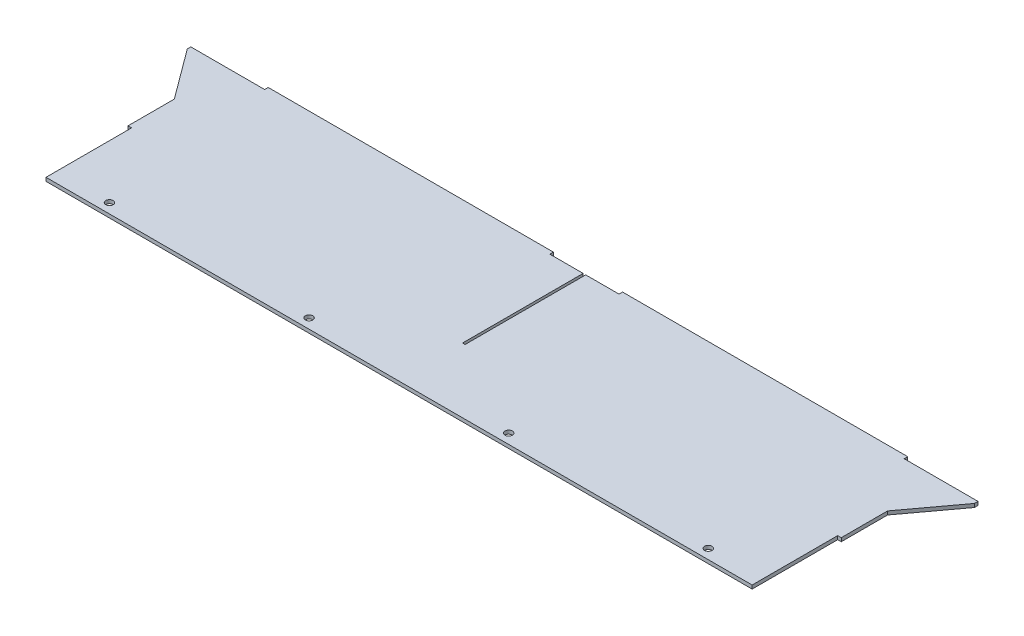
SolidWorks part; units mm, degrees
material "6061-T6 (SS)"
ref_plane "X-Y Datum" through (0, 0, 0) normal (0, 0, 1) x (1, 0, 0)
ref_plane "X-Z Datum" through (0, 0, 0) normal (0, 1, 0) x (1, 0, 0)
ref_plane "Y-Z Datum" through (0, 0, 0) normal (1, 0, 0) x (0, 0, -1)
sketch "Sketch1" plane through (0, 0, 0) normal (0, 1, 0) x (1, 0, 0)
  line L1 (-317.6778, 82.55) -> (317.6778, 82.55)
  line L2 (-317.6778, 82.55) -> (-317.6778, -82.55)
  line L3 (-317.6778, -82.55) -> (317.6778, -82.55)
  line L4 (317.6778, 82.55) -> (317.6778, -82.55)
  line L5 (-317.6778, 82.55) -> (317.6778, -82.55) construction
  line L6 (-317.6778, -82.55) -> (317.6778, 82.55) construction
  point P0 (0, 0)
  dimension "D1" = 635.3556
  dimension "D2" = 165.1
extrude "Boss-Extrude1" add sketch "Sketch1" along normal mid plane 3.175
sketch "Sketch2" plane through (0, 0, -82.55) normal (0, 0, -1) x (-1, 0, 0)
  line L20 (-317.6778, -1.5875) -> (317.6778, -1.5875) construction
  line L21 (-284.8229, -1.5875) -> (-30.8229, -1.5875)
  line L22 (30.8229, -1.5875) -> (284.8229, -1.5875)
  line L40 (30.8229, -1.5875) -> (30.8229, 1.5875)
  line L41 (30.8229, 1.5875) -> (284.8229, 1.5875)
  line L42 (284.8229, 1.5875) -> (284.8229, -1.5875)
  line L56 (-284.8229, -1.5875) -> (-284.8229, 1.5875)
  line L57 (-284.8229, 1.5875) -> (-30.8229, 1.5875)
  line L58 (-30.8229, 1.5875) -> (-30.8229, -1.5875)
extrude "Boss-Extrude2" add sketch "Sketch2" along normal blind 3.175
sketch "Sketch3" plane through (0, -1.5875, 0) normal (0, -1, 0) x (1, 0, 0)
  line L0 (317.6778, -82.55) -> (350.5784, -82.55)
  line L1 (350.5784, -82.55) -> (350.5784, -79.375)
  line L3 (350.5784, -79.375) -> (317.6778, -34.925)
  line L4 (317.6778, 82.55) -> (317.6778, -82.55) construction
  line L17 (317.6778, -82.55) -> (317.6778, 82.55)
  line L18 (317.6778, 82.55) -> (-317.6778, 82.55)
  line L19 (-317.6778, 82.55) -> (-317.6778, -82.55)
  line L20 (-317.6778, -82.55) -> (-284.8229, -82.55)
  line L21 (-284.8229, -82.55) -> (-284.8229, -85.725)
  line L22 (-284.8229, -85.725) -> (-30.8229, -85.725)
  line L23 (-30.8229, -85.725) -> (-30.8229, -82.55)
  line L24 (-30.8229, -82.55) -> (30.8229, -82.55)
  line L25 (30.8229, -82.55) -> (30.8229, -85.725)
  line L26 (30.8229, -85.725) -> (284.8229, -85.725)
  line L27 (284.8229, -85.725) -> (284.8229, -82.55)
  line L28 (284.8229, -82.55) -> (317.6778, -82.55)
  line L29 (317.6778, -82.55) -> (317.6778, -34.925)
  dimension "D1" = 32.9006
  dimension "D2" = 3.175
  dimension "D3" = 44.45
  dimension "D4" = 0
extrude "Boss-Extrude3" add sketch "Sketch3" against normal blind 3.175
mirror "Mirror1" about plane through (0, 0, 0) normal (1, 0, 0) of "Boss-Extrude3"
sketch "Sketch4" plane through (0, -1.5875, 0) normal (0, -1, 0) x (1, 0, 0)
  line L0 (-284.4038, 82.55) -> (-284.4038, 71.882)
  line L1 (-317.6778, 82.55) -> (317.6778, 82.55) construction
  line L2 (-284.4038, 71.882) -> (-317.6778, 71.882)
  line L3 (-317.6778, -34.925) -> (-317.6778, 82.55) construction
  circle A0 centre (-284.4038, 71.882) radius 3.675
extrude "Cut-Extrude1" [suppressed] cut sketch "Sketch4" against normal through all contours L2 A0 L0 | L0 A0 L2
pattern_linear "LPattern1" [suppressed] count 5 spacing 139.7 of bodies 107
sketch "Sketch5" plane through (0, -1.5875, 0) normal (0, -1, 0) x (1, 0, 0)
  line L0 (-317.6778, 82.55) -> (317.6778, 82.55) construction
  line L1 (-317.6778, -34.925) -> (-317.6778, 82.55) construction
  line L2 (-317.6778, 82.55) -> (317.6778, 82.55)
  line L3 (-317.6778, -34.925) -> (-317.6778, 82.55)
  line L4 (0, 127.4245) -> (0, -127.4245) construction
  line L5 (-317.6778, 82.55) -> (-314.5028, 82.55)
  line L6 (-317.6778, 82.55) -> (-317.6778, 6.35)
  line L7 (-317.6778, 6.35) -> (-314.5028, 6.35)
  line L8 (-314.5028, 82.55) -> (-314.5028, 6.35)
  line L9 (317.6778, 6.35) -> (314.5028, 6.35)
  line L10 (314.5028, 82.55) -> (314.5028, 6.35)
  line L11 (317.6778, -34.925) -> (317.6778, 82.55)
  line L12 (30.8229, -82.55) -> (-30.8229, -82.55) construction
  line L13 (30.8229, -82.55) -> (-30.8229, -82.55)
  line L14 (-1.143, -85.725) -> (-1.143, -82.55) construction
  line L15 (-1.143, -85.725) -> (-1.143, -82.55)
  line L17 (-1.143, -82.55) -> (1.143, -82.55)
  line L18 (-1.143, -82.55) -> (-1.143, 24.892)
  line L19 (-1.143, 24.892) -> (1.143, 24.892)
  line L20 (1.143, -82.55) -> (1.143, 24.892)
  point P10 (0, 0)
  line M10 (317.6778, -34.925) -> (317.6778, 82.55)
  line M11 (317.6778, 82.55) -> (-317.6778, 82.55)
  line M12 (-317.6778, 82.55) -> (-317.6778, -34.925)
  dimension "D1" = 3.175
  dimension "D2" = 76.2
  dimension "D3" = 2.286
  dimension "D4" = 107.442
extrude "Cut-Extrude2" cut sketch "Sketch5" against normal through all contours L19 L4 L17 L20 | L4 L19 L18 L13 | L8 L2 L7 M12 | L10 L9 M11 M10 region at (316.0903, -1.5875, 44.45) region at (0.5715, -1.5875, -28.829) region at (-0.5715, -1.5875, -28.829) region at (-316.0903, -1.5875, 44.45)
sketch "Sketch6" plane through (0, -1.5875, 0) normal (0, -1, 0) x (1, 0, 0)
  line L0 (-314.5028, 82.55) -> (314.5028, 82.55) construction
  line L1 (-314.5028, 82.55) -> (314.5028, 82.55)
  line L2 (0, 127.6954) -> (0, 37.4046) construction
  line L3 (314.5028, 82.55) -> (314.5028, 6.35) construction
  circle A0 centre (266.7, 73.8124) radius 3
  point P6 (0, 82.55)
  dimension "D1" = 6
  dimension "D2" = 8.7376
  dimension "D3" = 47.8028
hole_wizard "M6 Clearance Hole1" positions "Sketch7" profile "Sketch8" hole size "M6" standard "ANSI Metric" end condition through all
sketch "Sketch7" plane through (0, 1.5875, 0) normal (0, 1, 0) x (1, 0, 0)
  point P0 (266.7, -73.8124)
sketch "Sketch8" plane through (266.7, 1.5875, 73.8124) normal (1, 0, 0) x (0, 0, 1)
  line L0 (0, 0) -> (0, 3.175)
  line L1 (0, 3.175) -> (3.3, 3.175)
  line L2 (3.3, 3.175) -> (3.3, 0)
  line L5 (3.3, 0) -> (0, 0)
  line L11 (0, -6.35) -> (0, 107.95) construction
  dimension "Thru Hole Dia." = 6.6
  dimension "Thru Hole Depth" = 3.175
pattern_linear "LPattern2" count 4 spacing 177.8 along (-1, 0, 0) of "M6 Clearance Hole1"
